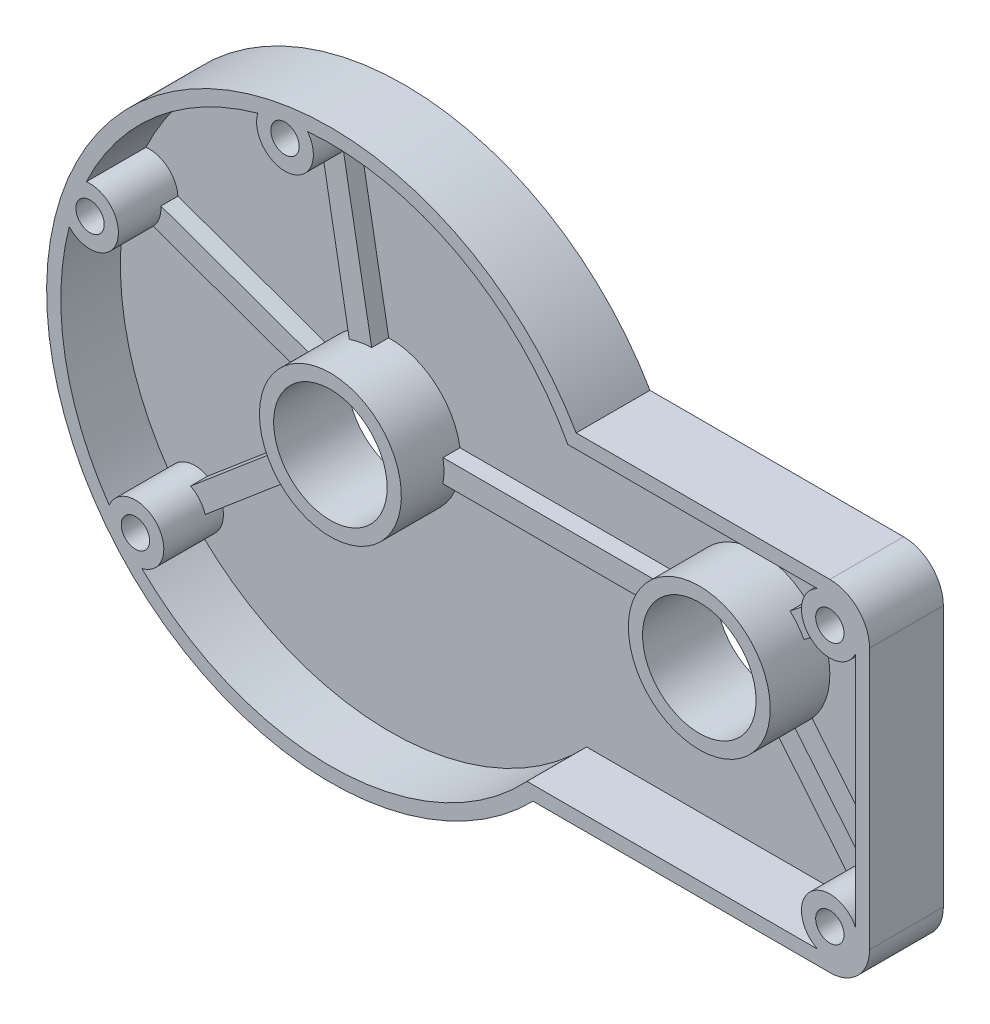
SolidWorks part; units mm, degrees
material "1060 Alloy"
ref_plane "Front Plane" through (0, 0, 0) normal (0, 0, 1) x (1, 0, 0)
ref_plane "Top Plane" through (0, 0, 0) normal (0, 1, 0) x (1, 0, 0)
ref_plane "Right Plane" through (0, 0, 0) normal (1, 0, 0) x (0, 0, -1)
sketch "Sketch1" plane through (0, 0, 0) normal (0, 0, 1) x (1, 0, 0)
  line L0 (0, 56.0587) -> (0, -58.9937) construction
  line L1 (43.3013, 25) -> (88, 25)
  line L3 (35.7071, -35) -> (88, -35)
  line L4 (95, 18) -> (95, -28)
  circle A0 centre (0, 0) radius 10
  arc A1 (43.3013, 25) -> (35.7071, -35) centre (0, 0) ccw
  circle A2 centre (0, 0) radius 45 construction
  circle A3 centre (65, 0) radius 10
  circle A4 centre (-8, 44.2832) radius 2.5
  circle A5 centre (-42.3504, 15.2134) radius 2.5
  circle A6 centre (-34.3504, -29.0698) radius 2.5
  arc A7 (88, 25) -> (95, 18) centre (88, 18) cw
  arc A8 (88, -35) -> (95, -28) centre (88, -28) ccw
  circle A9 centre (88, 18) radius 2.5
  circle A10 centre (88, -28) radius 2.5
  dimension "D1" = 20
  dimension "D2" = 5
  dimension "D3" = 5
  dimension "D4" = 100
  dimension "D5" = 7
  dimension "D10" = 35
  dimension "D6" = 60
  dimension "D7" = 60
  dimension "D8" = 65
  dimension "D9" = 60
  dimension "D11" = 95
  dimension "D12" = 8
extrude "Extrude1" add sketch "Sketch1" against normal blind 13
shell "Shell1" thickness 2.5 removed face at (90.5, -28, 0)
ref_plane "Plane1" through (0, 0, -7.5) normal (0, 0, 1) x (1, 0, 0)
sketch "Sketch2" plane through (0, 0, -7.5) normal (0, 0, 1) x (1, 0, 0)
  line L0 (-8, 44.2832) -> (-1.7778, 9.8407)
  line L1 (-9.4112, 3.3808) -> (-42.3504, 15.2134)
  line L2 (-34.3504, -29.0698) -> (-7.6334, -6.46)
  line L3 (10, 0) -> (55, 0)
  line L4 (72.8751, 6.1631) -> (88, 18)
  line L5 (71.3474, -7.7273) -> (88, -28)
  line L6 (-42.3504, 15.2134) -> (0, 0) construction
  line L7 (0, 0) -> (-8, 44.2832) construction
  line L8 (-8, 44.2832) -> (0, 0) construction
  line L9 (0, 0) -> (65, 0) construction
  line L10 (65, 0) -> (88, 18) construction
  line L11 (88, 18) -> (65, 0) construction
  line L12 (65, 0) -> (88, -28) construction
  line L14 (0, 0) -> (-34.3504, -29.0698) construction
  circle A1 centre (0, 0) radius 10 construction
  circle A3 centre (65, 0) radius 10 construction
  circle A4 centre (65, 0) radius 10 construction
  circle A6 centre (0, 0) radius 10 construction
rib "Rib1" sketch "Sketch2" sketch "Sketch2" thickness 4 extrusion direction normal to sketch draft on no parameters "D1"=4
